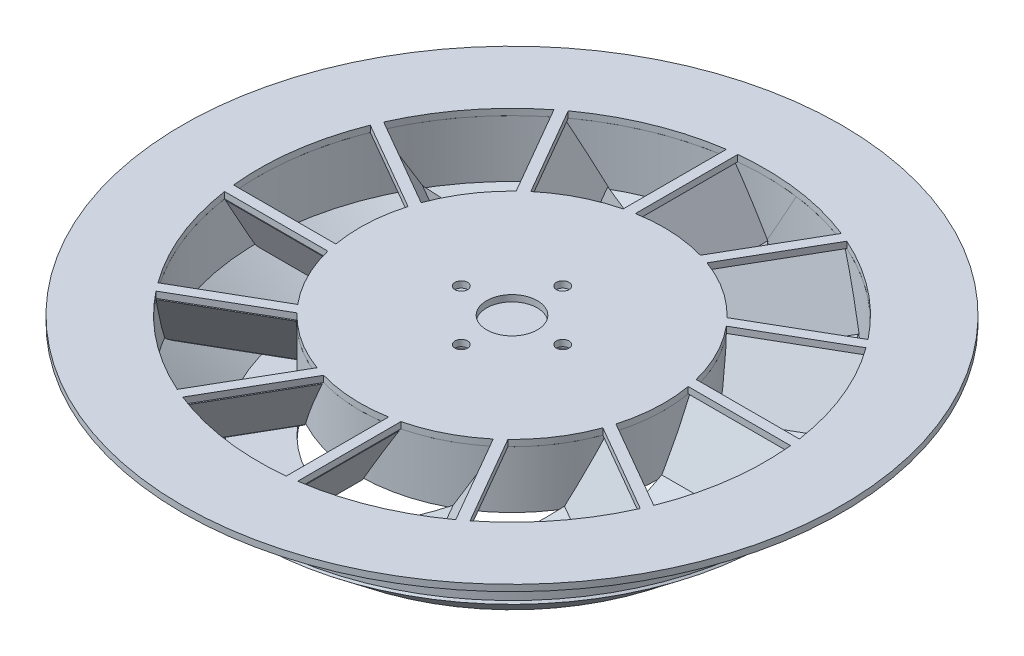
SolidWorks part; units mm, degrees
ref_plane "Front Plane" through (0, 0, 0) normal (0, 0, 1) x (1, 0, 0)
ref_plane "Top Plane" through (0, 0, 0) normal (0, 1, 0) x (1, 0, 0)
ref_plane "Right Plane" through (0, 0, 0) normal (1, 0, 0) x (0, 0, -1)
ref_plane "Plane1" through (0, -10.16, 0) normal (0, 1, 0) x (1, 0, 0)
sketch "Sketch3" plane through (0, 0, 0) normal (0, 1, 0) x (1, 0, 0)
  circle A11 centre (0, 0) radius 38.1
  circle A12 centre (0, 0) radius 6.35
  point P17 (0, 0)
  point P47 (0, 0)
  point P70 (0, 0)
  dimension "D1" = 76.2
  dimension "D2" = 12.7
extrude "Boss-Extrude3" add sketch "Sketch3" along normal blind 1.5875 contours A12 region at (-37.0224, 0, 0)
sketch "Sketch4" plane through (0, -10.16, 0) normal (0, 1, 0) x (1, 0, 0)
  circle A0 centre (0, 0) radius 38.1 construction
  circle A5 centre (0, 0) radius 38.1
  circle A6 centre (0, 0) radius 50.8
  dimension "D1" = 101.6
extrude "Boss-Extrude4" add sketch "Sketch4" against normal blind 1.5875 separate body
sketch "Sketch5" plane through (0, 0, 0) normal (1, 0, 0) x (0, 0, -1)
  line L16 (50.8, -10.16) -> (-50.8, -10.16) construction
  line L17 (50.8, -10.16) -> (-50.8, -10.16)
  line L18 (0, 0) -> (63.5, 0) construction
  line L19 (63.5, 0) -> (50.8, -10.16)
  line L20 (63.5, 0) -> (64.4917, -1.2396)
  line L21 (50.8, -10.16) -> (51.7917, -11.3996)
  line L22 (64.4917, -1.2396) -> (51.7917, -11.3996)
  dimension "D1" = 63.5
  dimension "D2" = 1.5875
ref_axis "Axis1" through (0, -12.4143, 0) along (0, 1, 0)
revolve "Revolve1" add sketch "Sketch5" angle 360 about axis through (0, -12.4143, 0) along (0, 1, 0)
ref_axis "Axis2" through (0, 0, -83.82) along (0, 0, 1)
ref_plane "Plane3" through (0, 0, 0) normal (0.5, -0.866, 0) x (0, 0, 1)
split line "Split Line2"
sketch "Sketch10" plane through (0, 0, 0) normal (0.5, -0.866, 0) x (0, 0, 1)
  line L2 (63.5, 0) -> (38.1, 0)
  line L3 (38.1, 0) -> (38.1, -14.8015) construction
  line L4 (47.6546, 20.32) -> (33.7925, 20.32) construction
  line L5 (47.6546, 20.32) -> (33.7925, 20.32)
  arc A1 (38.1, 0) -> (33.7925, 20.32) centre (-11.9821, 0) ccw
  ellipse E0 centre (0, 5.08) end of major axis (-38.1, 5.08) minor radius 32.9956 (33.7925, 20.32) -> (-33.7925, 20.32) ccw construction
  ellipse E1 centre (0, -110.4348) end of major axis (0, -263.4577) minor radius 91.734 (63.5, 0) -> (47.6546, 20.32) ccw construction
  ellipse E2 centre (0, -110.4348) end of major axis (0, -263.4577) minor radius 91.734 (63.5, 0) -> (47.6546, 20.32) ccw
  ellipse E3 centre (0, 5.08) end of major axis (-38.1, 5.08) minor radius 32.9956 (33.7925, 20.32) -> (-33.7925, 20.32) ccw construction
  point P12 (0, 0)
  point P29 (0, 0)
  dimension "D1" = 25.4
extrude "Boss-Extrude7" add sketch "Sketch10" along normal blind 0.7937 and the other way blind 0.7937 separate body
pattern_circular "CirPattern1" count 12 every 30 about axis through (0, -12.4143, 0) along (0, 1, 0) of bodies 111
sketch "Sketch11" plane through (0, 1.5875, 0) normal (0, 1, 0) x (1, 0, 0)
  circle A0 centre (0, 0) radius 38.1
  circle A1 centre (0, 0) radius 63.5
  circle A2 centre (0, 0) radius 36.5125
  circle A3 centre (0, 0) radius 65.0875
  dimension "D1" = 127
  dimension "D2" = 130.175
  dimension "D3" = 76.2
  dimension "D4" = 73.025
extrude "Boss-Extrude9" add sketch "Sketch11" along normal blind 12.7 and the other way blind 1.5875 contours A0 A2 | A3 A1 region at (-37.0224, 1.5875, 0) region at (-64.9034, 1.5875, 0)
ref_plane "Plane4" through (0, 0, 0) normal (-0.866, 0.5, 0) x (0, 0, 1)
split line "Split Line3"
sketch "Sketch13" plane through (0, 0, 0) normal (-0.866, 0.5, 0) x (0, 0, 1)
  line L0 (37.1963, 16.4978) -> (62.9619, 16.4978)
  line L1 (63.5, 0) -> (38.1, 0)
  ellipse E2 centre (0, 0) end of major axis (0, 127) minor radius 63.5 (63.5, 0) -> (62.9619, 16.4978) ccw construction
  ellipse E3 centre (0, 0) end of major axis (0, -76.2) minor radius 38.1 (38.1, 0) -> (37.1963, 16.4978) ccw construction
  ellipse E4 centre (0, 0) end of major axis (0, 127) minor radius 63.5 (63.5, 0) -> (62.9619, 16.4978) ccw
  ellipse E5 centre (0, 0) end of major axis (0, -76.2) minor radius 38.1 (38.1, 0) -> (37.1963, 16.4978) ccw
  point P8 (0, 0)
  point P11 (63.4934, 0.4725)
extrude "Boss-Extrude10" add sketch "Sketch13" along normal blind 0.7937 and the other way blind 0.7937 separate body
pattern_circular "CirPattern4" count 12 over 360 about axis through (0, -12.4143, 0) along (0, 1, 0) of bodies 130
sketch "Sketch14" plane through (0, 14.2875, 0) normal (0, 1, 0) x (1, 0, 0)
  line L0 (-7.5615, 62.9619) -> (-7.5615, 37.1963) construction
  line L1 (-7.5615, 62.9619) -> (-7.5615, 37.1963) construction
  line L2 (-6.609, 63.1551) -> (-6.609, 37.5224)
  line L3 (-9.149, 62.8375) -> (-9.149, 36.9852)
  line L4 (25.854, 57.9984) -> (13.0377, 35.7999)
  line L5 (23.4955, 58.9933) -> (10.5694, 36.6046)
  line L6 (51.3895, 37.3011) -> (29.1909, 24.4848)
  line L7 (49.8443, 39.342) -> (27.4556, 26.4159)
  line L8 (63.1551, 6.609) -> (37.5224, 6.609)
  line L9 (62.8375, 9.149) -> (36.9852, 9.149)
  line L10 (57.9984, -25.854) -> (35.7999, -13.0377)
  line L11 (58.9933, -23.4955) -> (36.6046, -10.5694)
  line L12 (37.3011, -51.3895) -> (24.4848, -29.1909)
  line L13 (39.342, -49.8443) -> (26.4159, -27.4556)
  line L14 (6.609, -63.1551) -> (6.609, -37.5224)
  line L15 (9.149, -62.8375) -> (9.149, -36.9852)
  line L16 (-25.854, -57.9984) -> (-13.0377, -35.7999)
  line L17 (-23.4955, -58.9933) -> (-10.5694, -36.6046)
  line L18 (-51.3895, -37.3011) -> (-29.1909, -24.4848)
  line L19 (-49.8443, -39.342) -> (-27.4556, -26.4159)
  line L20 (-63.1551, -6.609) -> (-37.5224, -6.609)
  line L21 (-62.8375, -9.149) -> (-36.9852, -9.149)
  line L22 (-57.9984, 25.854) -> (-35.7999, 13.0377)
  line L23 (-58.9933, 23.4955) -> (-36.6046, 10.5694)
  line L24 (-37.3011, 51.3895) -> (-24.4848, 29.1909)
  line L25 (-39.342, 49.8443) -> (-26.4159, 27.4556)
  circle A0 centre (0, 0) radius 6.35 construction
  circle A1 centre (0, 0) radius 6.35
  arc A2 (8.2489, -37.1963) -> (8.2489, 37.1963) centre (0, 0) ccw
  arc A3 (8.2489, 37.1963) -> (8.2489, -37.1963) centre (0, 0) ccw
  arc A4 (9.149, -36.9852) -> (24.4848, -29.1909) centre (0, 0) ccw
  arc A5 (8.2489, 37.1963) -> (-6.609, 37.5224) centre (0, 0) ccw
  arc A6 (-9.149, 62.8375) -> (-37.3011, 51.3895) centre (0, 0) ccw
  arc A9 (-9.149, 36.9852) -> (-24.4848, 29.1909) centre (0, 0) ccw
  arc A10 (-26.4159, 27.4556) -> (-35.7999, 13.0377) centre (0, 0) ccw
  arc A11 (-39.342, 49.8443) -> (-57.9984, 25.854) centre (0, 0) ccw
  arc A12 (23.4955, 58.9933) -> (-6.609, 63.1551) centre (0, 0) ccw
  arc A13 (49.8443, 39.342) -> (25.854, 57.9984) centre (0, 0) ccw
  arc A14 (62.8375, 9.149) -> (51.3895, 37.3011) centre (0, 0) ccw
  arc A15 (58.9933, -23.4955) -> (63.1551, 6.609) centre (0, 0) ccw
  arc A16 (39.342, -49.8443) -> (57.9984, -25.854) centre (0, 0) ccw
  arc A17 (9.149, -62.8375) -> (37.3011, -51.3895) centre (0, 0) ccw
  arc A18 (-23.4955, -58.9933) -> (6.609, -63.1551) centre (0, 0) ccw
  arc A19 (-49.8443, -39.342) -> (-25.854, -57.9984) centre (0, 0) ccw
  arc A20 (-62.8375, -9.149) -> (-51.3895, -37.3011) centre (0, 0) ccw
  arc A21 (-58.9933, 23.4955) -> (-63.1551, -6.609) centre (0, 0) ccw
  arc A22 (-36.6046, 10.5694) -> (-37.5224, -6.609) centre (0, 0) ccw
  arc A23 (-36.9852, -9.149) -> (-29.1909, -24.4848) centre (0, 0) ccw
  arc A24 (-27.4556, -26.4159) -> (-13.0377, -35.7999) centre (0, 0) ccw
  arc A25 (-10.5694, -36.6046) -> (6.609, -37.5224) centre (0, 0) ccw
  arc A26 (26.4159, -27.4556) -> (35.7999, -13.0377) centre (0, 0) ccw
  arc A27 (36.6046, -10.5694) -> (37.5224, 6.609) centre (0, 0) ccw
  arc A28 (36.9852, 9.149) -> (29.1909, 24.4848) centre (0, 0) ccw
  arc A29 (27.4556, 26.4159) -> (13.0377, 35.7999) centre (0, 0) ccw
  arc A30 (10.5694, 36.6046) -> (8.2489, 37.1963) centre (0, 0) ccw
  circle A31 centre (0, 0) radius 82.55
  point P63 (0, 0)
  dimension "D3" = 127
  dimension "D7" = 165.1
  dimension "D4" = 2.54
  dimension "D5" = 1.5875
  dimension "D1" = 0
  dimension "D6" = 12
extrude "Boss-Extrude12" add sketch "Sketch14" along normal blind 1.5875 separate body
sketch "Sketch15" plane through (0, 0, 0) normal (0, -1, 0) x (1, 0, 0)
  line L0 (0, 0) -> (12.7, 0) construction
  line L1 (0, 0) -> (0, -12.7) construction
  line L2 (0, 0) -> (-12.7, 0) construction
  line L3 (0, 0) -> (0, 12.7) construction
  point P9 (0, 0)
  dimension "D1" = 12.7
  dimension "D2" = 4
hole_wizard "Hole1" positions "3DSketch1" profile "Sketch16" legacy end condition through all
sketch3d "3DSketch1"
  point P0 (-12.7, 0, 0)
  point P3 (0, 0, 12.7)
  point P6 (12.7, 0, 0)
  point P9 (0, 0, -12.7)
sketch "Sketch16" plane through (-12.7, 0, 0) normal (1, 0, 0) x (0, 0, -1)
  line L0 (0, 0) -> (0, 15.875)
  line L1 (0, 15.875) -> (1.5875, 15.875)
  line L2 (1.5875, 15.875) -> (1.5875, 6.35)
  line L3 (1.5875, 6.35) -> (3.175, 6.35)
  line L4 (3.175, 6.35) -> (3.175, 0)
  line L5 (3.175, 0) -> (0, 0)
  line L6 (0, 110) -> (0, -10) construction
  dimension "Diameter" = 3.175
  dimension "Depth" = 15.875
  dimension "C-Bore Diameter" = 6.35
  dimension "C-Bore Depth" = 6.35
